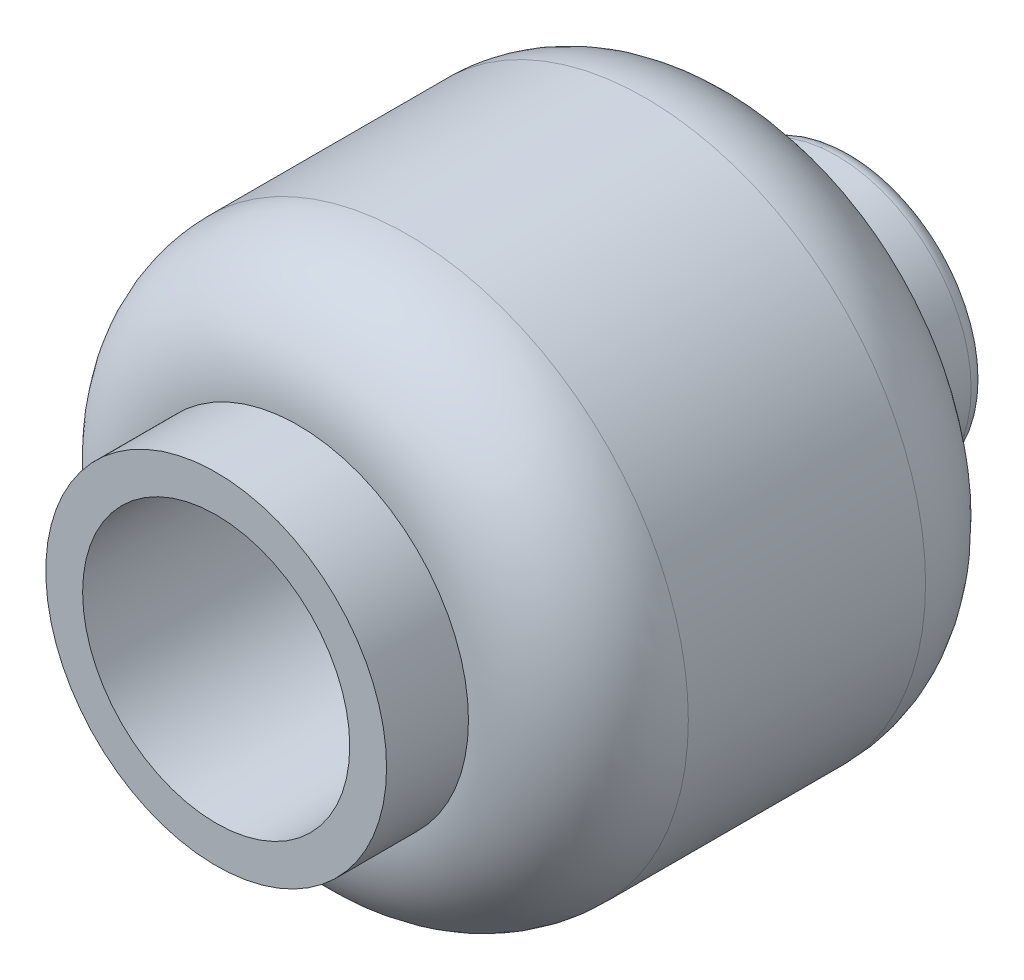
SolidWorks part; units mm, degrees
ref_plane "Front Plane" through (0, 0, 0) normal (0, 0, 1) x (1, 0, 0)
ref_plane "Top Plane" through (0, 0, 0) normal (0, 1, 0) x (1, 0, 0)
ref_plane "Right Plane" through (0, 0, 0) normal (1, 0, 0) x (0, 0, -1)
sketch "Sketch1" plane through (0, 0, 0) normal (0, 1, 0) x (1, 0, 0)
  line L0 (0, 0) -> (0, 294.2844) construction
  line L1 (-78.74, 0) -> (-61.722, 0)
  line L2 (-78.74, 0) -> (-78.74, 37.846)
  line L3 (0, 294.2844) -> (-62.23, 294.2844)
  line L4 (-62.23, 294.2844) -> (-62.23, 249.0724)
  line L5 (-62.23, 249.0724) -> (-129.54, 249.0724)
  line L6 (-129.54, 249.0724) -> (-129.54, 37.846)
  line L7 (-129.54, 37.846) -> (-78.74, 37.846)
  line L8 (-61.722, 0) -> (-61.722, 147.1422)
  line L9 (-61.722, 147.1422) -> (0, 147.1422)
  line L10 (0, 294.2844) -> (0, 147.1422)
  dimension "D1" = 294.2844
  dimension "D2" = 129.54
  dimension "D3" = 37.846
  dimension "D4" = 45.212
  dimension "D5" = 50.8
  dimension "D6" = 61.722
  dimension "D7" = 147.1422
  dimension "D8" = 62.23
revolve "Revolve1" add sketch "Sketch1" angle 360 about L0
fillet "Fillet2" radius 50.8 2 edges at (129.54, 0, -37.846) (129.54, 0, -249.0724)
fillet "Fillet3" radius 7.62 1 edges at (62.23, 0, -294.2844)
